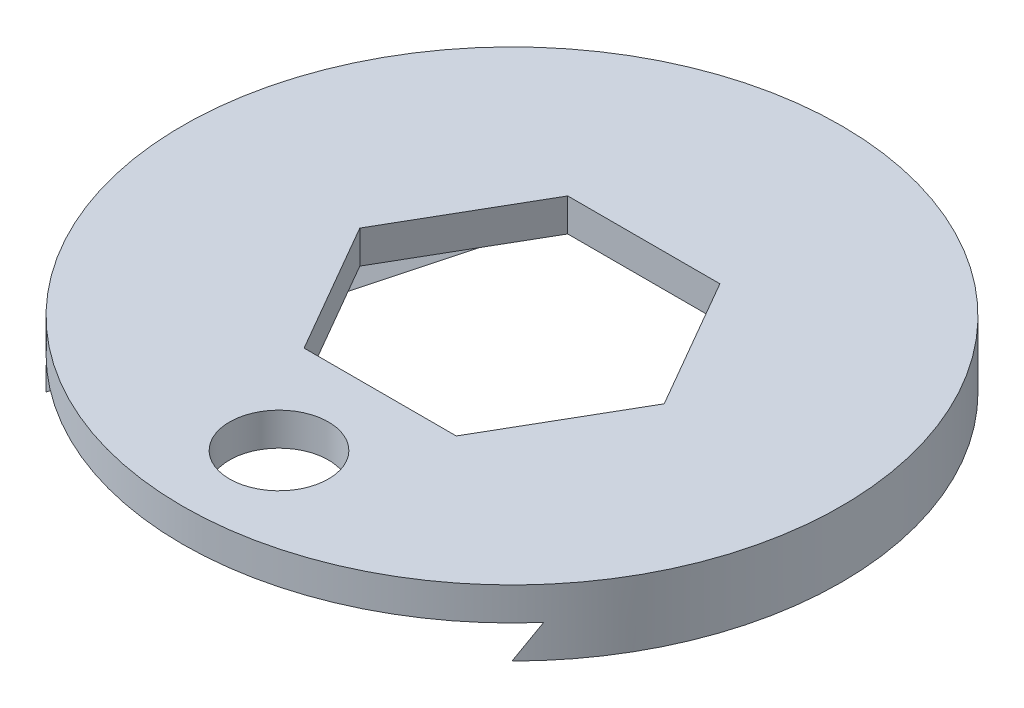
SolidWorks part; units mm, degrees
ref_plane "Front Plane" through (0, 0, 0) normal (0, 0, 1) x (1, 0, 0)
ref_plane "Top Plane" through (0, 0, 0) normal (0, 1, 0) x (1, 0, 0)
ref_plane "Right Plane" through (0, 0, 0) normal (1, 0, 0) x (0, 0, -1)
sketch "Sketch1" plane through (0, 0, 0) normal (0, 1, 0) x (1, 0, 0)
  line L0 (-35.3553, -35.3553) -> (-12.941, 48.2963)
  line L1 (-35.3553, -35.3553) -> (35.3553, -35.3553) construction
  line L2 (-35.3553, -35.3553) -> (-35.3553, 35.3553) construction
  line L3 (-35.3553, 35.3553) -> (35.3553, 35.3553) construction
  line L4 (35.3553, -35.3553) -> (35.3553, 35.3553) construction
  line L5 (-35.3553, -35.3553) -> (35.3553, 35.3553) construction
  line L6 (-35.3553, 35.3553) -> (35.3553, -35.3553) construction
  line L7 (0, 96.5926) -> (0, -94.4212) construction
  line L8 (35.3553, -35.3553) -> (12.941, 48.2963)
  circle A0 centre (0, 0) radius 50
  circle A1 centre (0, -35.3553) radius 7.5
  dimension "D1" = 100
  dimension "D3" = 15
  dimension "D2" = 15
extrude "Boss-Extrude1" add sketch "Sketch1" along normal blind 5 contours A0
extrude "Boss-Extrude2" add sketch "Sketch1<5>" against normal blind 5 contours L8 A0 | L0 A0 region at (-34.0499, 0, -9.1236) region at (34.0499, 0, -9.1236)
sketch "Sketch1<5>" plane through (0, 0, 0) normal (0, 1, 0) x (1, 0, 0) same geometry as "Sketch1"
draft "Draft1" type of draft neutral plane draft angle 30 faces to draft 2 face at (24.1481, -2.5, -6.4705) face at (-24.1481, -2.5, -6.4705) neutral plane through (0, -5, 0) neutral plane normal (0, -1, 0) reverse direction yes parameters "D1"=30
extrude "Cut-Extrude2" cut sketch "Sketch1<8>" against normal through all both and the other way through all contours A1 region at (0, 0, 35.3553)
sketch "Sketch1<8>" plane through (0, 0, 0) normal (0, 1, 0) x (1, 0, 0) same geometry as "Sketch1"
sketch "Sketch2" plane through (0, 0, 0) normal (0, -1, 0) x (1, 0, 0)
  line L1 (23.094, 0) -> (11.547, 20)
  line L2 (11.547, 20) -> (-11.547, 20)
  line L3 (-11.547, 20) -> (-23.094, 0)
  line L4 (-23.094, 0) -> (-11.547, -20)
  line L5 (-11.547, -20) -> (11.547, -20)
  line L6 (11.547, -20) -> (23.094, 0)
  circle A0 centre (0, 0) radius 20 construction
extrude "Cut-Extrude3" cut sketch "Sketch2" against normal through all
